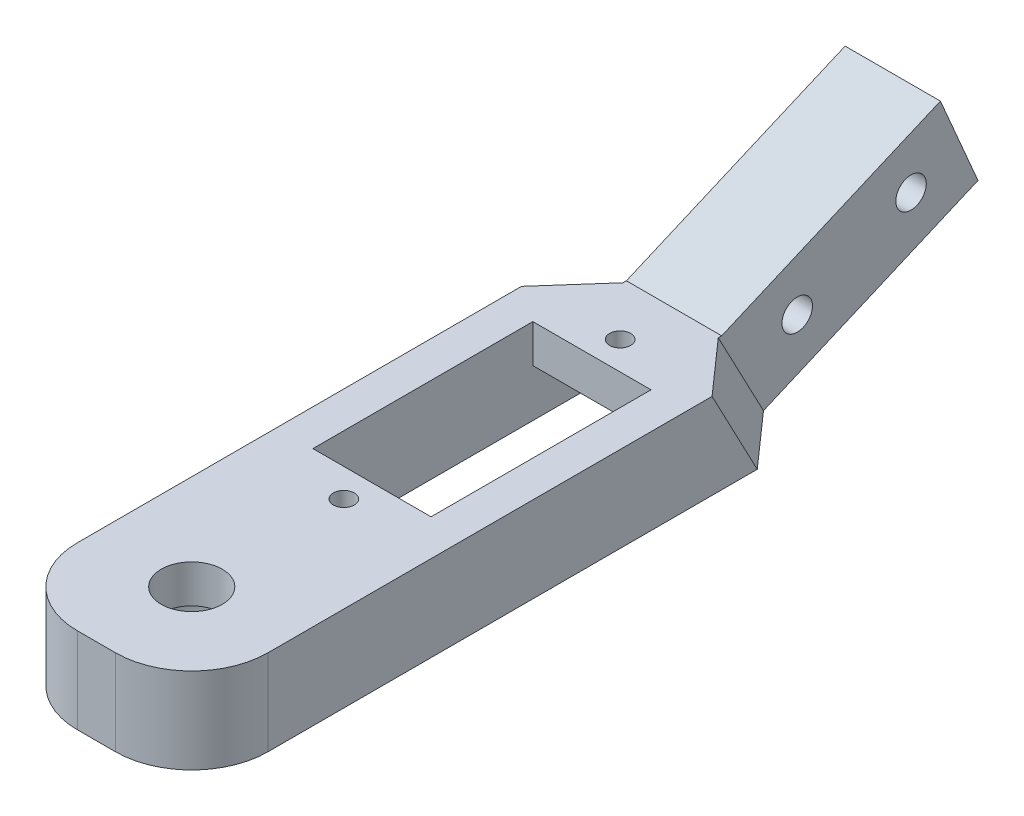
SolidWorks part; units mm, degrees
ref_plane "前视基准面" through (0, 0, 0) normal (0, 0, 1) x (1, 0, 0)
ref_plane "上视基准面" through (0, 0, 0) normal (0, 1, 0) x (1, 0, 0)
ref_plane "右视基准面" through (0, 0, 0) normal (1, 0, 0) x (0, 0, -1)
sketch "草图1" plane through (0, 0, 0) normal (1, 0, 0) x (0, 0, -1)
  line L0 (55, -4) -> (50.2563, 5)
  line L1 (55, -4) -> (-10, -4)
  line L3 (50.2563, 5) -> (-10, 5)
  line L4 (-10, -4) -> (-10, 5)
  line L5 (55, -4) -> (-10, 5) construction
  line L6 (55, 5) -> (-10, -4) construction
  point P0 (22.5, 0.5)
extrude "凸台-拉伸1" add sketch "草图1" along normal mid plane 20
sketch "草图2" plane through (0, -4, 0) normal (0, 1, 0) x (1, 0, 0)
  circle A0 centre (0, 0) radius 6.7
extrude "切除-拉伸1" cut sketch "草图2" along normal blind 5
sketch "草图4" plane through (0, 1, 0) normal (0, -1, 0) x (1, 0, 0)
  circle A0 centre (0, 0) radius 3.2
extrude "切除-拉伸3" cut sketch "草图4" against normal through all
sketch "草图3" plane through (0, 5, 0) normal (0, 1, 0) x (1, 0, 0)
  line L1 (6.2, 42) -> (-6.2, 42)
  line L2 (6.2, 42) -> (6.2, 18.9147)
  line L3 (6.2, 18.9147) -> (-6.2, 18.9147)
  line L4 (-6.2, 42) -> (-6.2, 18.9147)
  line L5 (6.2, 42) -> (-6.2, 18.9147) construction
  line L6 (6.2, 18.9147) -> (-6.2, 42) construction
  point P0 (0, 30.4574)
extrude "切除-拉伸2" cut sketch "草图3" against normal through all
sketch "草图5" plane through (0, -4, 0) normal (0, -1, 0) x (1, 0, 0)
  line L1 (6.2, -47.9147) -> (-6.2, -47.9147)
  line L2 (6.2, -47.9147) -> (6.2, -13)
  line L3 (6.2, -13) -> (-6.2, -13)
  line L4 (-6.2, -47.9147) -> (-6.2, -13)
  line L5 (6.2, -47.9147) -> (-6.2, -13) construction
  line L6 (6.2, -13) -> (-6.2, -47.9147) construction
  line L7 (-6.2, -42) -> (-6.2, -18.9147) construction
  line L8 (-6.2, -18.9147) -> (6.2, -18.9147) construction
  point P0 (0, -30.4574)
  point P8 (-6.2, -30.4574)
  point P11 (0, -18.9147)
extrude "切除-拉伸4" cut sketch "草图5" against normal offset from surface (5 mm away) 4 up to face at (0, 5, -30.4574)
sketch "草图6" plane through (0, 1, 0) normal (0, -1, 0) x (1, 0, 0)
  line L0 (-6.2, -30.4574) -> (6.2, -30.4574) construction
  line L1 (-6.2, -47.9147) -> (-6.2, -13) construction
  line L2 (6.2, -13) -> (6.2, -47.9147) construction
  line L3 (0, -30.4574) -> (0, -15.9574) construction
  circle A0 centre (0, -15.9574) radius 1.1
  circle A2 centre (0, -44.9574) radius 1.1
extrude "切除-拉伸5" cut sketch "草图6" against normal through all
fillet "圆角1" radius 8 2 edges at (-10, 0.5, 10) (10, 0.5, 10)
sketch "草图7" plane through (10, 0, 0) normal (1, 0, 0) x (0, 0, -1)
  line L0 (31.0016, 0) -> (51.0016, 0) construction
  circle A0 centre (51.0016, 0) radius 1.6
  circle A1 centre (31.0016, 0) radius 1.6
extrude "切除-拉伸6" [suppressed] cut sketch "草图7" against normal through all
sketch "草图8" [suppressed] plane through (-6.2, 0, 0) normal (1, 0, 0) x (0, 0, -1)
  circle A0 centre (31.0016, 0) radius 3
extrude "切除-拉伸7" [suppressed] cut sketch "草图8" against normal blind 2
mirror "镜向1" [suppressed] about plane through (0, 0, 0) normal (1, 0, 0)
sketch "草图9" plane through (0, 0, 0) normal (1, 0, 0) x (0, 0, -1)
  line L0 (53.191, -4.7767) -> (71.9218, 3.2656) construction
  line L1 (55, -4) -> (77.5126, 5.6661)
  line L2 (77.5126, 5.6661) -> (73.5672, 14.8549)
  line L3 (73.5672, 14.8549) -> (50.6149, 5)
  line L4 (50.2563, 5) -> (-2, 5) construction
  line L7 (75.5399, 10.2605) -> (53.199, 0.6681) construction
  line L8 (50.6149, 5) -> (50.2563, 5)
  line L9 (50.2563, 5) -> (55, -4)
  line L10 (55, -4) -> (46.3441, 16.1597) construction
  circle A0 centre (70.4861, 8.0906) radius 1.6
  circle A1 centre (58.5406, 2.9616) radius 1.6
  point P1 (55, -4)
  point P6 (75.5399, 10.2605)
  dimension "D1" = 13
  dimension "D2" = 3.2
  dimension "D3" = 3.2
  dimension "D4" = 10
  dimension "D5" = 5.5
  dimension "D6" = 6
extrude "凸台-拉伸2" add sketch "草图9" along normal mid plane 10
chamfer "倒角2" distance 5 angle 45 2 edges at (-10, 0.5, -52.6282) (10, 0.5, -52.6282)
